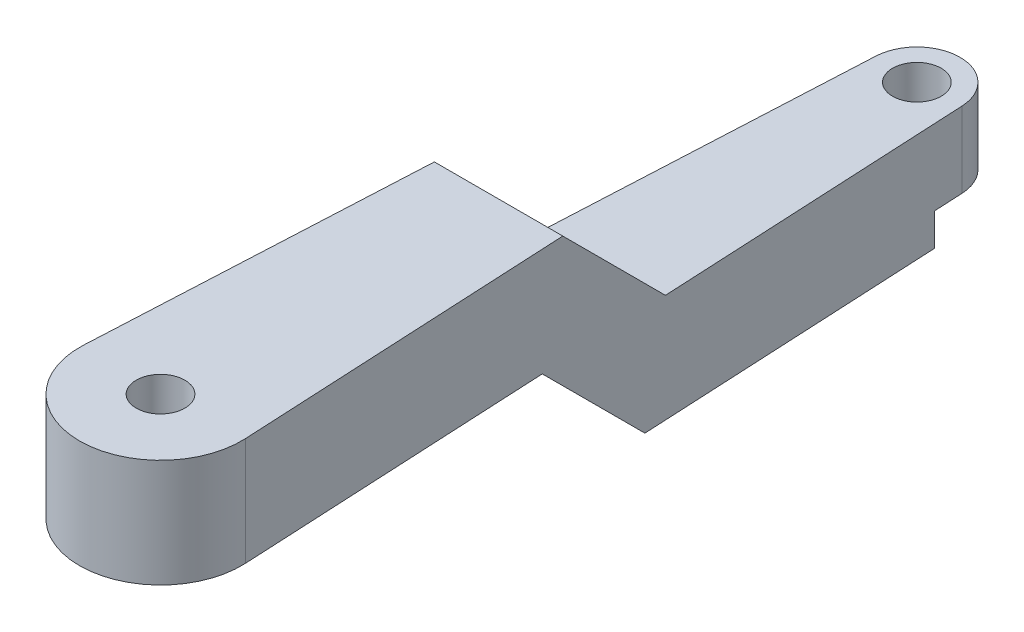
SolidWorks part; units mm, degrees
ref_plane "Front Plane" through (0, 0, 0) normal (0, 0, 1) x (1, 0, 0)
ref_plane "Top Plane" through (0, 0, 0) normal (0, 1, 0) x (1, 0, 0)
ref_plane "Right Plane" through (0, 0, 0) normal (1, 0, 0) x (0, 0, -1)
sketch "Sketch1" plane through (0, 0, 0) normal (0, 1, 0) x (1, 0, 0)
  line L0 (0, 0) -> (0, 35) construction
  line L1 (-3.7453, 0.1875) -> (-1.9975, 35.1)
  line L2 (3.7453, 0.1875) -> (1.9975, 35.1)
  circle A0 centre (0, 35) radius 2
  circle A1 centre (0, 0) radius 3.75
  circle A2 centre (0, 35) radius 1.125
  circle A3 centre (0, 0) radius 1.125
  dimension "D1" = 4
  dimension "D2" = 7.5
  dimension "D4" = 2.25
  dimension "D5" = 2.25
  dimension "D3" = 35
extrude "Boss-Extrude1" add sketch "Sketch1" along normal blind 10 contours L0 A1 L2 A0 | A1 L0 A0 L1 | A3 A1 | A0 A2 region at (2.5114, 0, -2.6403) region at (-1.493, 0, -16.8592) region at (1.493, 0, -16.8592) region at (-1.4081, 0, -33.6606)
sketch "Sketch2" plane through (0, 10, 0) normal (0, 1, 0) x (1, 0, 0)
  line L0 (-2.8714, 17.6438) -> (2.8714, 17.6438) construction
  line L1 (-3.7453, 0.1875) -> (-1.9975, 35.1) construction
  line L2 (3.7453, 0.1875) -> (1.9975, 35.1) construction
  line L3 (-2.8714, 17.6438) -> (-1.9975, 35.1)
  line L4 (2.8714, 17.6438) -> (1.9975, 35.1)
  line L5 (-2.8714, 17.6438) -> (-3.7453, 0.1875)
  line L6 (2.8714, 17.6438) -> (3.7453, 0.1875)
  line L7 (-6, 20.6438) -> (6, 20.6438)
  line L8 (-5.6415, 14.6438) -> (6.3585, 14.6438)
  circle A0 centre (0, 35) radius 2
  circle A1 centre (0, 35) radius 1.125
  circle A2 centre (0, 35) radius 1.125 construction
  circle A3 centre (0, 0) radius 3.75
  circle A4 centre (0, 0) radius 1.125
  circle A5 centre (0, 0) radius 1.125 construction
  point P30 (0, 20.6438)
  point P31 (0, 17.6438)
  line M1 (-1.9975, 35.1) -> (-3.7453, 0.1875)
  arc M2 (-3.7453, 0.1875) -> (3.7453, 0.1875) centre (0, 0) ccw
  line M3 (3.7453, 0.1875) -> (1.9975, 35.1)
  arc M4 (1.9975, 35.1) -> (-1.9975, 35.1) centre (0, 35) ccw
  circle M5 centre (0, 35) radius 1.125
  circle M6 centre (0, 0) radius 1.125
  dimension "D1" = 12
  dimension "D2" = 12
  dimension "D3" = 3
  dimension "D4" = 3
extrude "Cut-Extrude1" cut sketch "Sketch2" against normal blind 5 contours A0 L0 M1 M3 | A0 M4 M5 region at (0, 10, -26.7744) region at (0, 10, -36.9434)
extrude "Cut-Extrude3" cut sketch "Sketch2<4>" along normal blind 5 from surface contours A3 M2 M6 | A3 L8 L5 M3 region at (0, 10, -8.6232) region at (0, 10, -3.6439) starting at face at (0, 0, -17.1344)
sketch "Sketch2<4>" plane through (0, 10, 0) normal (0, 1, 0) x (1, 0, 0) same geometry as "Sketch2"
chamfer "Chamfer1" distance 5 angle 45 2 edges at (0, 0, -14.6438) (0, 10, -20.6438)
sketch "Sketch3" plane through (0, 0, 0) normal (0, -1, 0) x (1, 0, 0)
  line L1 (0, -32.5463) -> (-2.125, -33.7731)
  line L2 (-2.125, -33.7731) -> (-2.125, -36.2269)
  line L3 (-2.125, -36.2269) -> (0, -37.4537)
  line L4 (0, -37.4537) -> (2.125, -36.2269)
  line L5 (2.125, -36.2269) -> (2.125, -33.7731)
  line L6 (2.125, -33.7731) -> (0, -32.5463)
  circle A0 centre (0, -35) radius 2.125 construction
  dimension "D1" = 4.25
extrude "Cut-Extrude4" cut sketch "Sketch3" against normal blind 1.5
